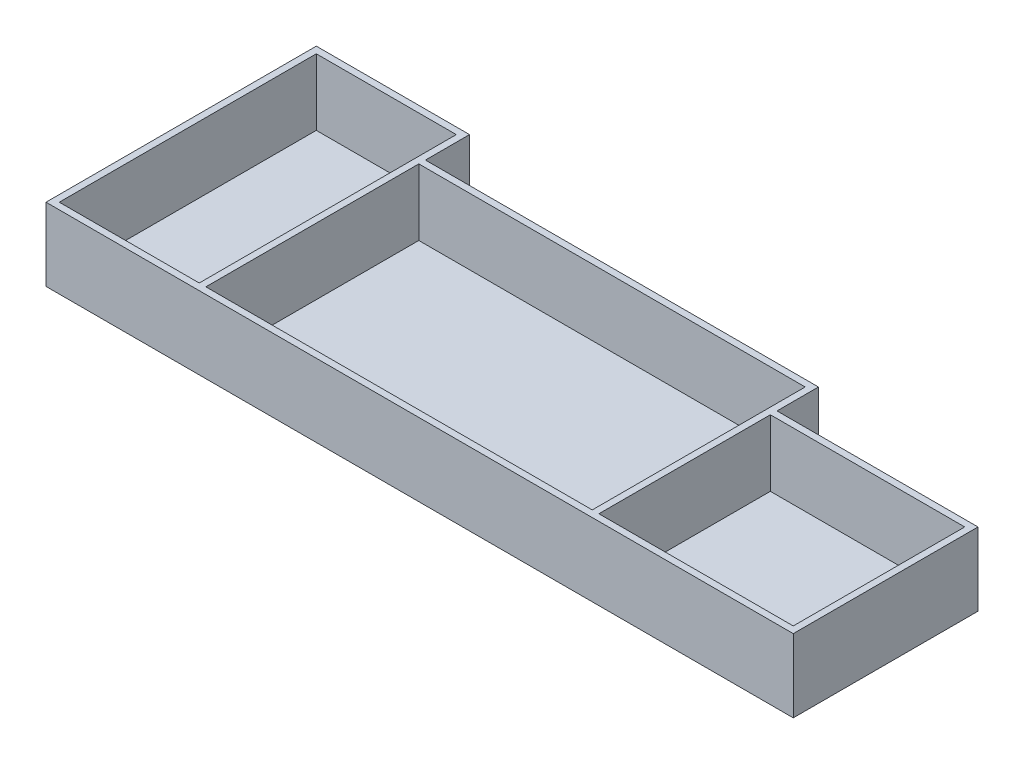
SolidWorks part; units mm, degrees
ref_plane "Front Plane" through (0, 0, 0) normal (0, 0, 1) x (1, 0, 0)
ref_plane "Top Plane" through (0, 0, 0) normal (0, 1, 0) x (1, 0, 0)
ref_plane "Right Plane" through (0, 0, 0) normal (1, 0, 0) x (0, 0, -1)
sketch "Sketch1" plane through (0, 0, 0) normal (0, 1, 0) x (1, 0, 0)
  line L0 (2, 79.5) -> (44.2, 79.5)
  line L1 (0, 0) -> (2, 0)
  line L2 (0, 0) -> (0, 2)
  line L6 (0, 2) -> (0, 79.5)
  line L8 (2, 2) -> (2, 79.5)
  line L10 (0, 79.5) -> (0, 81.5)
  line L11 (0, 81.5) -> (2, 81.5)
  line L13 (2, 2) -> (44.2, 2)
  line L15 (2, 0) -> (44.2, 0)
  line L17 (44.2, 0) -> (46.2, 0)
  line L21 (46.2, 2) -> (162.7, 2)
  line L23 (46.2, 0) -> (162.7, 0)
  line L27 (162.7, 0) -> (164.7, 0)
  line L29 (164.7, 2) -> (223.3, 2)
  line L31 (164.7, 0) -> (223.3, 0)
  line L34 (223.3, 2) -> (223.3, 0)
  line L35 (223.3, 0) -> (225.3, 0)
  line L36 (225.3, 2) -> (225.3, 0)
  line L38 (44.2, 2) -> (44.2, 66.2)
  line L40 (46.2, 2) -> (46.2, 66.2)
  line L44 (44.2, 66.2) -> (44.2, 68.2)
  line L46 (162.7, 2) -> (162.7, 53.7)
  line L48 (164.7, 2) -> (164.7, 53.7)
  line L52 (162.7, 53.7) -> (162.7, 55.7)
  line L53 (44.2, 79.5) -> (44.2, 68.2)
  line L54 (2, 81.5) -> (46.2, 81.5)
  line L55 (46.2, 81.5) -> (46.2, 68.2)
  line L56 (46.2, 68.2) -> (164.7, 68.2)
  line L57 (164.7, 68.2) -> (164.7, 55.7)
  line L58 (46.2, 66.2) -> (162.7, 66.2)
  line L59 (162.7, 66.2) -> (162.7, 55.7)
  line L60 (164.7, 55.7) -> (225.3, 55.7)
  line L61 (225.3, 55.7) -> (225.3, 2)
  line L62 (223.3, 2) -> (223.3, 53.7)
  line L63 (223.3, 53.7) -> (164.7, 53.7)
  point P38 (0, 0)
  dimension "D1" = 77.5
  dimension "D2" = 64.2
  dimension "D3" = 51.7
  dimension "D4" = 42.2
  dimension "D5" = 116.5
  dimension "D6" = 58.6
  dimension "D7" = 2
  dimension "D8" = 2
  dimension "D9" = 2
  dimension "D10" = 2
extrude "Boss-Extrude1" add sketch "Sketch1" against normal blind 2 contours L53 L0 L8 L13 L38 L44 | L62 L63 L48 L29 | L63 L62 L35 L36 L61 L60 L57 L56 L55 L54 L11 L10 L6 L2 L1 L15 L17 L23 L27 L31 L29 L48 L0 L53 L44 L38 L13 L8 L58 L59 L52 L46 L21 L40 | L59 L58 L40 L21 L46 L52 region at (23.1, 0, -40.75) region at (194, 0, -27.85) region at (2.3959, 0, -1) region at (104.45, 0, -34.1)
extrude "Boss-Extrude2" add sketch "Sketch1<4>" along normal blind 20 contours L63 L62 L35 L36 L61 L60 L57 L56 L55 L54 L11 L10 L6 L2 L1 L15 L17 L23 L27 L31 L29 L48 L0 L53 L44 L38 L13 L8 L58 L59 L52 L46 L21 L40 region at (2.3959, 0, -1)
sketch "Sketch1<4>" plane through (0, 0, 0) normal (0, 1, 0) x (1, 0, 0) same geometry as "Sketch1"
